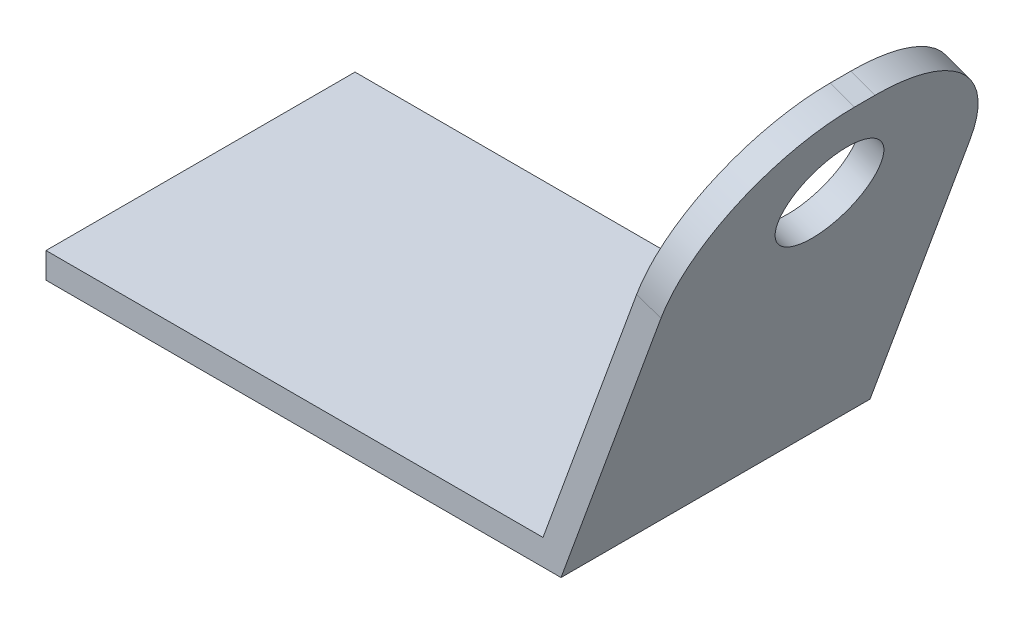
SolidWorks part; units mm, degrees
ref_plane "Front Plane" through (0, 0, 0) normal (0, 0, 1) x (1, 0, 0)
ref_plane "Top Plane" through (0, 0, 0) normal (0, 1, 0) x (1, 0, 0)
ref_plane "Right Plane" through (0, 0, 0) normal (1, 0, 0) x (0, 0, -1)
sketch "Sketch1" plane through (0, 0, 0) normal (0, 1, 0) x (1, 0, 0)
  line L1 (-31.75, -19.05) -> (31.75, -19.05)
  line L2 (-31.75, -19.05) -> (-31.75, 19.05)
  line L3 (-31.75, 19.05) -> (31.75, 19.05)
  line L4 (31.75, -19.05) -> (31.75, 19.05)
  line L5 (-31.75, -19.05) -> (31.75, 19.05) construction
  line L6 (-31.75, 19.05) -> (31.75, -19.05) construction
  point P0 (0, 0)
  dimension "D1" = 63.5
  dimension "D2" = 38.1
extrude "Boss-Extrude1" add sketch "Sketch1" along normal blind 3.175
sketch "Sketch2" plane through (0, 0, 19.05) normal (0, 0, 1) x (1, 0, 0)
  line L0 (31.75, 0) -> (50.145, 50.54)
  line L1 (31.75, 0) -> (28.7665, 1.0859)
  line L2 (50.145, 50.54) -> (47.1615, 51.6259)
  line L3 (28.7665, 1.0859) -> (47.1615, 51.6259)
  line L4 (31.75, 0) -> (47.1615, 51.6259) construction
  line L5 (50.145, 50.54) -> (28.7665, 1.0859) construction
  line L6 (31.75, 3.175) -> (31.75, 0) construction
  line L7 (-31.75, 0) -> (31.75, 0) construction
  point P1 (39.4558, 25.8129)
  dimension "D1" = 20
  dimension "D2" = 50.8
extrude "Boss-Extrude2" add sketch "Sketch2" against normal up to surface (38.1 mm away) up to face at (0, 1.5875, -19.05)
sketch "Sketch3" plane through (25.0524, -9.1183, 0) normal (-0.9397, 0.342, 0) x (0, 0, 1)
  line L0 (0, 51.9427) -> (0, 64.6427) construction
  line L1 (-19.05, 64.6427) -> (19.05, 64.6427) construction
  circle A0 centre (0, 51.9427) radius 6.35
  dimension "D2" = 12.7
  dimension "D1" = 12.7
extrude "Cut-Extrude1" cut sketch "Sketch3" against normal through all
fillet "Fillet1" radius 17.78 2 edges at (48.6533, 51.0829, 19.05) (48.6533, 51.0829, -19.05)
